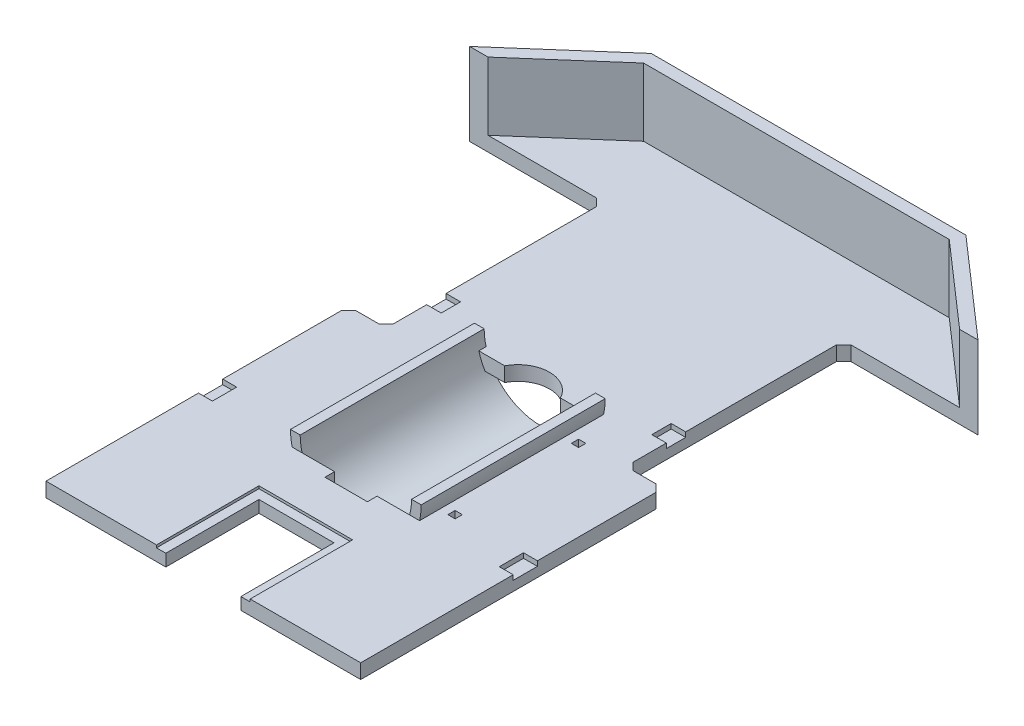
SolidWorks part; units mm, degrees
ref_plane "Front Plane" through (0, 0, 0) normal (0, 0, 1) x (1, 0, 0)
ref_plane "Top Plane" through (0, 0, 0) normal (0, 1, 0) x (1, 0, 0)
ref_plane "Right Plane" through (0, 0, 0) normal (1, 0, 0) x (0, 0, -1)
sketch "Sketch1" plane through (0, 0, 0) normal (0, 1, 0) x (1, 0, 0)
  line L8 (65, 0) -> (-65, 0)
  line L9 (-65, 0) -> (-105, -35)
  line L10 (-105, -35) -> (-65, -35)
  line L11 (-65, -35) -> (-65, -250)
  line L12 (-65, -250) -> (65, -250)
  line L13 (0, 0) -> (0, -50000) construction
  line L14 (65, -35) -> (65, -250)
  line L15 (105, -35) -> (65, -35)
  line L16 (65, 0) -> (105, -35)
  point P18 (0, -250)
  point P21 (0, 0)
  dimension "D1" = 250
  dimension "D2" = 35
  dimension "D3" = 40
  dimension "D4" = 65
extrude "Boss-Extrude1" add sketch "Sketch1" along normal blind 6 contours L8 L13 L12 L14 L15 L16 | L13 L8 L9 L10 L11 L12 | L12 L14 L15 L16 L8 L9 L10 L11 region at (34.3928, 0, 120.8014) region at (-34.3928, 0, 120.8014)
sketch "Sketch2" plane through (0, 6, 0) normal (0, 1, 0) x (1, 0, 0)
  line L0 (-105, -35) -> (-65, -35) construction
  line L1 (105, -35) -> (65, -35) construction
  line L2 (65, 0) -> (105, -35) construction
  line L3 (65, 0) -> (-65, 0) construction
  line L4 (-65, 0) -> (-105, -35) construction
  line L5 (-105, -35) -> (-97.407, -35)
  line L6 (101.7075, -38.7629) -> (63.1213, -5)
  line L7 (63.1213, -5) -> (-63.1213, -5)
  line L8 (-63.1213, -5) -> (-101.7075, -38.7629)
  line L9 (97.407, -35) -> (63.1213, -5)
  line L10 (63.1213, -5) -> (-63.1213, -5)
  line L11 (-63.1213, -5) -> (-97.407, -35)
  line L12 (105, -35) -> (97.407, -35)
  line L13 (65, 0) -> (105, -35)
  line L14 (65, 0) -> (-65, 0)
  line L15 (-65, 0) -> (-105, -35)
  dimension "D1" = 5
extrude "Boss-Extrude2" add sketch "Sketch2" along normal blind 28 contours L9 L10 L11 L5 L15 L14 L13 L12
sketch "Sketch5" plane through (0, 6, 0) normal (0, 1, 0) x (1, 0, 0)
  line L0 (-65, -35) -> (-65, -250) construction
  line L1 (-65, -35) -> (-49.5, -35)
  line L2 (-65, -35) -> (-65, -125)
  line L3 (-65, -125) -> (-49.5, -125)
  line L4 (-49.5, -35) -> (-49.5, -125)
  line L6 (0, 24.2773) -> (0, -269.599) construction
  line L7 (65, -125) -> (49.5, -125)
  line L8 (49.5, -35) -> (49.5, -125)
  line L9 (65, -35) -> (49.5, -35)
  line L10 (65, -35) -> (65, -125)
  line L11 (-97.407, -35) -> (-65, -35) construction
  dimension "D2" = 90
  dimension "D3" = 15.5
extrude "Cut-Extrude2" cut sketch "Sketch5" against normal through all
chamfer "Chamfer2" distance 3 6 edges at (49.5, 3, 35) (-49.5, 3, 35) (-65, 3, 125) (65, 3, 125) (49.5, 3, 125) (-49.5, 3, 125)
sketch "Sketch8" plane through (0, 6, 0) normal (0, 1, 0) x (1, 0, 0)
  line L1 (-23, -114) -> (23, -114)
  line L2 (-23, -114) -> (-23, -187)
  line L3 (-23, -187) -> (23, -187)
  line L4 (23, -114) -> (23, -187)
  line L5 (-65, -250) -> (65, -250) construction
  line L6 (-62, -125) -> (-52.5, -125) construction
  point P8 (0, -250)
  point P9 (0, -187)
  dimension "D1" = 73
  dimension "D2" = 46
  dimension "D3" = 11
extrude "Cut-Extrude4" cut sketch "Sketch8" against normal blind 23 contours L2 L1 L4 L3
sketch "Sketch9" plane through (0, 0, 0) normal (0, 0, 1) x (1, 0, 0)
  line L2 (-27, 12) -> (-23, 12)
  line L3 (23, 12) -> (27, 12)
  arc A0 (-23, 12) -> (23, 12) centre (0, 12) ccw
  arc A1 (-27, 12) -> (27, 12) centre (0, 12) ccw
  dimension "D1" = 23
  dimension "D2" = 4
  dimension "D3" = 12
extrude "Boss-Extrude5" add sketch "Sketch9" along normal up to surface (187 mm away) and the other way blind 3 from surface contours L3 A1 L2 A0 up to face at (0, 3, 187) starting at face at (0, 3, 114)
sketch "Sketch10" plane through (0, 6, 0) normal (0, 1, 0) x (1, 0, 0)
  line L0 (-19.35, -250) -> (-19.35, -207.69)
  line L1 (-19.35, -207.69) -> (19.35, -207.69)
  line L2 (19.35, -207.69) -> (19.35, -250)
  line L3 (19.35, -250) -> (15.5, -250)
  line L4 (15.5, -250) -> (15.5, -211.54)
  line L5 (15.5, -211.54) -> (-15.5, -211.54)
  line L6 (-15.5, -211.54) -> (-15.5, -250)
  line L7 (-15.5, -250) -> (-19.35, -250)
  line L8 (-65, -250) -> (65, -250) construction
  point P10 (0, -250)
  point P11 (0, -207.69)
  dimension "D1" = 3.85
  dimension "D2" = 3.85
  dimension "D3" = 38.7
  dimension "D4" = 42.31
extrude "Boss-Extrude6" add sketch "Sketch10" along normal blind 18.95 contours L7 L0 L1 L2 L3 L4 L5 L6
sketch "Sketch11" plane through (0, 6, 0) normal (0, 1, 0) x (1, 0, 0)
  line L4 (-15.5, -211.54) -> (-15.5, -250)
  line L5 (-15.5, -250) -> (15.5, -250)
  line L9 (-15.5, -250) -> (15.5, -250)
  line L18 (-15.5, -211.54) -> (-15.5, -250)
  line L20 (15.5, -250) -> (15.5, -211.54)
  line L21 (15.5, -250) -> (15.5, -211.54)
  line L22 (15.5, -211.54) -> (-15.5, -211.54)
  line L23 (15.5, -211.54) -> (-15.5, -211.54)
  dimension "D1" = 0
extrude "Cut-Extrude5" cut sketch "Sketch11" against normal blind 19.03
extrude "Cut-Extrude7" cut sketch "Sketch10<3>" against normal blind 20 from surface starting at face at (0, 24.95, 229.8075)
sketch "Sketch10<3>" plane through (0, 6, 0) normal (0, 1, 0) x (1, 0, 0) same geometry as "Sketch10"
sketch "Sketch12" plane through (0, 6, 0) normal (0, 1, 0) x (1, 0, 0)
  line L0 (-22.2036, -114) -> (22.2036, -114) construction
  line L1 (-11.5, -114) -> (11.5, -114)
  arc A0 (-11.5, -114) -> (11.5, -114) centre (0, -120) cw
  dimension "D1" = 6
  dimension "D2" = 23
extrude "Cut-Extrude8" cut sketch "Sketch12" against normal up to next
sketch "Sketch13" plane through (0, 6, 0) normal (0, 1, 0) x (1, 0, 0)
  line L0 (-19.6214, -187) -> (19.6214, -187) construction
  line L1 (-8.775, -187) -> (8.775, -187)
  line L2 (-8.775, -187) -> (-8.775, -191)
  line L3 (-8.775, -191) -> (8.775, -191)
  line L4 (8.775, -187) -> (8.775, -191)
  point P6 (0, -191)
  dimension "D1" = 17.55
  dimension "D2" = 4
extrude "Cut-Extrude9" cut sketch "Sketch13" against normal up to next
sketch "Sketch14" plane through (0, 6, 0) normal (0, 1, 0) x (1, 0, 0)
  line L0 (-62, -125) -> (-52.5, -125) construction
  line L1 (-33, -125) -> (-30, -125)
  line L2 (-33, -125) -> (-33, -128)
  line L3 (-33, -128) -> (-30, -128)
  line L4 (-30, -125) -> (-30, -128)
  line L5 (-33, -176) -> (-30, -176)
  line L6 (-33, -176) -> (-33, -179)
  line L7 (-33, -179) -> (-30, -179)
  line L8 (-30, -176) -> (-30, -179)
  line L9 (30, -125) -> (33, -125)
  line L10 (30, -125) -> (30, -128)
  line L11 (30, -128) -> (33, -128)
  line L12 (33, -125) -> (33, -128)
  line L13 (30, -176) -> (33, -176)
  line L14 (30, -176) -> (30, -179)
  line L15 (30, -179) -> (33, -179)
  line L16 (33, -176) -> (33, -179)
  line L17 (52.5, -125) -> (62, -125) construction
  dimension "D1" = 3
  dimension "D2" = 30
  dimension "D4" = 30
  dimension "D3" = 48
extrude "Cut-Extrude10" cut sketch "Sketch14" against normal up to next
sketch "Sketch15" plane through (0, 6, 0) normal (0, 1, 0) x (1, 0, 0)
  line L0 (-49.5, -122) -> (-49.5, -38) construction
  line L1 (-49.5, -100.2494) -> (-43.5, -100.2494)
  line L2 (-49.5, -100.2494) -> (-49.5, -108.2494)
  line L3 (-49.5, -108.2494) -> (-43.5, -108.2494)
  line L4 (-43.5, -100.2494) -> (-43.5, -108.2494)
  line L5 (-65, -128) -> (-65, -250) construction
  line L6 (-65, -177) -> (-59.25, -177)
  line L7 (-65, -177) -> (-65, -187)
  line L8 (-65, -187) -> (-59.25, -187)
  line L9 (-59.25, -177) -> (-59.25, -187)
  line L10 (0, 0) -> (0, -50000) construction
  line L11 (-22.2036, -114) -> (-11.5, -114) construction
  line L12 (-22.2036, -187) -> (-8.775, -187) construction
  line L13 (65, -187) -> (59.25, -187)
  line L14 (59.25, -177) -> (59.25, -187)
  line L15 (65, -177) -> (59.25, -177)
  line L16 (65, -177) -> (65, -187)
  line L17 (49.5, -108.2494) -> (43.5, -108.2494)
  line L18 (43.5, -100.2494) -> (43.5, -108.2494)
  line L19 (49.5, -100.2494) -> (43.5, -100.2494)
  line L20 (49.5, -100.2494) -> (49.5, -108.2494)
  dimension "D1" = 8
  dimension "D2" = 6
  dimension "D3" = 5.7506
  dimension "D4" = 10
  dimension "D5" = 5.75
extrude "Cut-Extrude11" cut sketch "Sketch15" against normal blind 2
